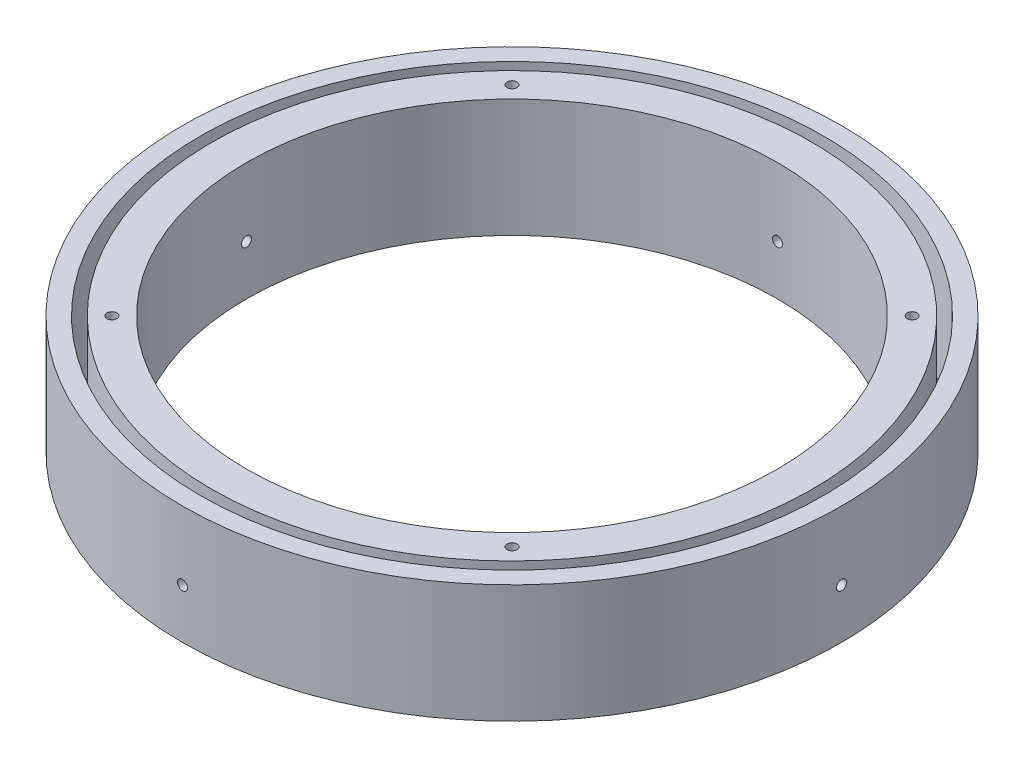
SolidWorks part; units mm, degrees
ref_plane "Front Plane" through (0, 0, 0) normal (0, 0, 1) x (1, 0, 0)
ref_plane "Top Plane" through (0, 0, 0) normal (0, 1, 0) x (1, 0, 0)
ref_plane "Right Plane" through (0, 0, 0) normal (1, 0, 0) x (0, 0, -1)
sketch "Sketch1" plane through (0, 0, 0) normal (0, 1, 0) x (1, 0, 0)
  circle A0 centre (0, 0) radius 106
  dimension "D1" = 212
extrude "Boss-Extrude1" add sketch "Sketch1" along normal blind 38
sketch "Sketch2" plane through (0, 38, 0) normal (0, 1, 0) x (1, 0, 0)
  circle A0 centre (0, 0) radius 100.2
  circle A1 centre (0, 0) radius 96.6
  dimension "D1" = 200.4
  dimension "D2" = 193.2
extrude "Cut-Extrude1" cut sketch "Sketch2" against normal blind 36
sketch "Sketch3" plane through (0, 38, 0) normal (0, 1, 0) x (1, 0, 0)
  circle A0 centre (0, 0) radius 85.4
  dimension "D1" = 170.8
extrude "Cut-Extrude2" cut sketch "Sketch3" against normal through all
sketch "Sketch5" plane through (0, 38, 0) normal (0, 1, 0) x (1, 0, 0)
  line L0 (0, 0) -> (-133.7584, 0) construction
  line L1 (0, 0) -> (-64.3467, 64.3467) construction
  circle A0 centre (0, 0) radius 91 construction
  circle A1 centre (-64.3467, 64.3467) radius 1.6
  circle A2 centre (64.3467, 64.3467) radius 1.6
  circle A3 centre (64.3467, -64.3467) radius 1.6
  circle A4 centre (-64.3467, -64.3467) radius 1.6
  point P15 (0, 0)
  dimension "D1" = 182
  dimension "D3" = 4
  dimension "D4" = 3.2
  dimension "D2" = 45
extrude "Cut-Extrude3" cut sketch "Sketch5" against normal through all
ref_plane "Plane1" through (0, 0, 86) normal (0, 0, 1) x (1, 0, 0)
sketch "Sketch6" plane through (0, 0, 86) normal (0, 0, 1) x (1, 0, 0)
  line L0 (-106, 0) -> (106, 0) construction
  circle A0 centre (0, 16) radius 1.6
  dimension "D2" = 3.2
  dimension "D1" = 16
extrude "Cut-Extrude4" cut sketch "Sketch6" along normal through all and the other way blind 8
pattern_circular "CirPattern1" count 4 every 90 about axis through (0, 38, 0) along (0, -1, 0) of "Cut-Extrude4"
sketch "Sketch7" plane through (0, 0, 86) normal (0, 0, 1) x (1, 0, 0)
  line L0 (-3.05, 17.7609) -> (-3.05, 37.7609)
  line L1 (0, 12.4782) -> (3.05, 14.2391)
  line L2 (3.05, 14.2391) -> (3.05, 17.7609)
  line L5 (-3.05, 17.7609) -> (-3.05, 14.2391)
  line L6 (-3.05, 14.2391) -> (0, 12.4782)
  line L7 (-3.05, 37.7609) -> (3.05, 37.7609)
  line L8 (3.05, 37.7609) -> (3.05, 17.7609)
  line L10 (0, 19.5218) -> (-1.525, 18.6414) [skipped]
  line L11 (3.05, 17.7609) -> (1.525, 18.6414) [skipped]
  arc A0 (-3.05, 16) -> (3.05, 16) centre (0, 16) ccw construction
  dimension "D1" = 6.1
  dimension "D2" = 20
extrude "Cut-Extrude5" cut sketch "Sketch7" along normal blind 2.8 from offset 3
pattern_circular "CirPattern2" count 4 every 90 about axis through (0, 38, 0) along (0, -1, 0) of "Cut-Extrude5"
